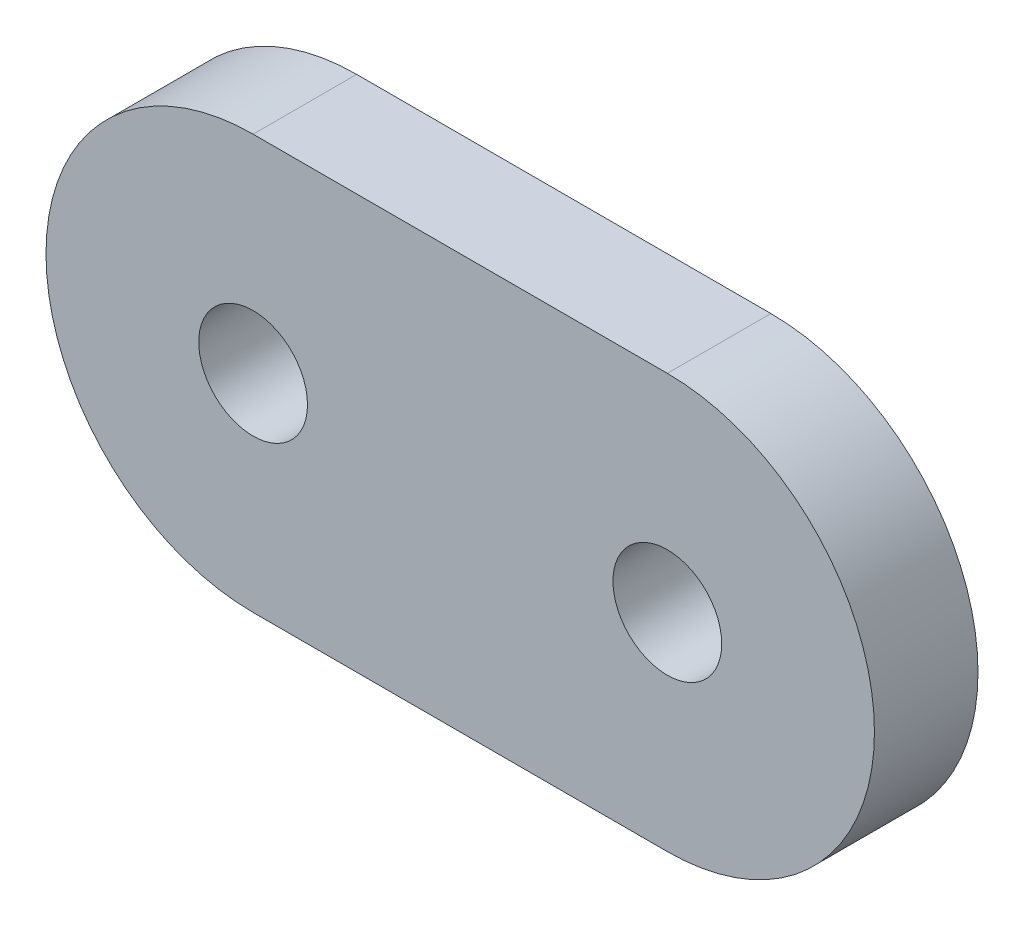
SolidWorks part; units mm, degrees
ref_plane "Alzado" through (0, 0, 0) normal (0, 0, 1) x (1, 0, 0)
ref_plane "Planta" through (0, 0, 0) normal (0, 1, 0) x (1, 0, 0)
ref_plane "Vista lateral" through (0, 0, 0) normal (1, 0, 0) x (0, 0, -1)
sketch "Croquis1" plane through (0, 0, 0) normal (0, 0, 1) x (1, 0, 0)
  line L0 (-19.9908, 0) -> (-3.9908, 0) construction
  line L1 (-19.9908, 8) -> (-3.9908, 8)
  line L2 (-19.9908, -8) -> (-3.9908, -8)
  arc A0 (-19.9908, 8) -> (-19.9908, -8) centre (-19.9908, 0) ccw
  arc A1 (-3.9908, -8) -> (-3.9908, 8) centre (-3.9908, 0) ccw
  point P3 (-11.9908, 0)
  dimension "D1" = 16
  dimension "D2" = 16
sheet metal parameters "Chapa metálica1" thickness 4 parameters "D1"=0.7366, "Espesor"=4
base flange "Brida base1" sketch "Croquis1" thickness 4 reverse thickness direction no parameters "D1"=0.7366
hole_wizard "Taladro roscado M51" positions "Croquis5" profile "Croquis4" tap size "M5" standard "Is"
sketch "Croquis5" plane through (0, 0, 0) normal (0, 0, 1) x (1, 0, 0)
  point P0 (-19.9908, 0)
  point P3 (-3.9908, 0)
sketch "Croquis4" plane through (-19.9908, 0, 0) normal (1, 0, 0) x (0, -1, 0)
  line L0 (0, 0) -> (0, 15.2618)
  line L1 (0, 15.2618) -> (2.1, 14)
  line L2 (2.1, 14) -> (2.1, 0)
  line L5 (2.1, 0) -> (0, 0)
  line L10 (0, 15.2618) -> (-2.1, 14) construction
  line L11 (0, -6.35) -> (0, 107.95) construction
  dimension "Diámetro de perforador para roscar" = 4.2
  dimension "Profundidad de perforador para roscar" = 14
  dimension "Ángulo de perforador" = 118
cosmetic thread "Rosca de taladro1" parameters "D1"=4, "D2"=5
cosmetic thread "Rosca de taladro2" parameters "D1"=4, "D2"=5
flat pattern "Chapa desplegada1" [suppressed]
sketch "Líneas de pliegue1" plane through (0, 0, 0) normal (0, 1, 0) x (1, 0, 0)
sketch "Cuadro delimitador1" [suppressed] plane through (0, 0, 0) normal (0, 1, 0) x (1, 0, 0)
